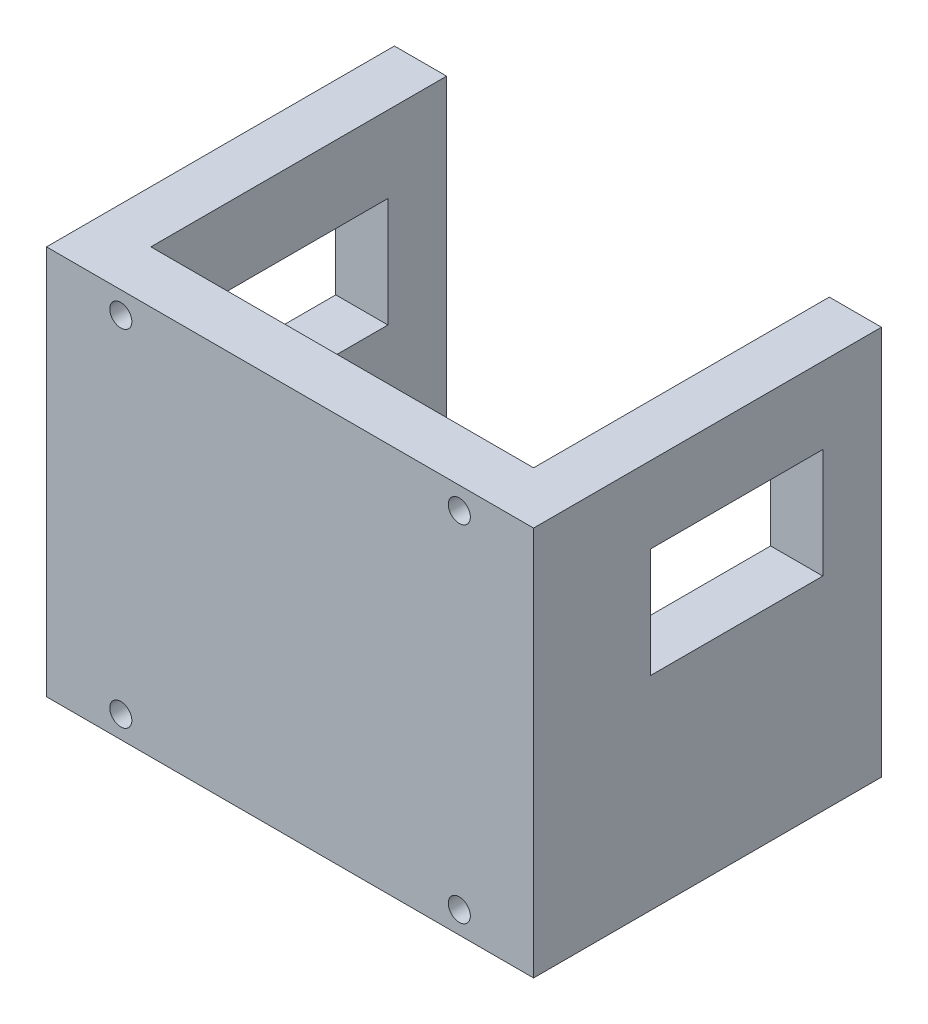
SolidWorks part; units mm, degrees
ref_plane "Plan de face" through (0, 0, 0) normal (0, 0, 1) x (1, 0, 0)
ref_plane "Plan de dessus" through (0, 0, 0) normal (0, 1, 0) x (1, 0, 0)
ref_plane "Plan de droite" through (0, 0, 0) normal (1, 0, 0) x (0, 0, -1)
sketch "Esquisse1" plane through (0, 0, 0) normal (0, 0, 1) x (1, 0, 0)
  line L0 (-109.5296, 4.4139) -> (30.4704, 4.4139)
  line L1 (-109.5296, 4.4139) -> (-109.5296, -107.5861)
  line L2 (-109.5296, -107.5861) -> (30.4704, -107.5861)
  line L3 (30.4704, -107.5861) -> (30.4704, 4.4139)
  point P4 (30.4704, 4.4139)
  dimension "D1" = 140
  dimension "D2" = 112
extrude "Boss.-Extru.1" add sketch "Esquisse1" along normal blind 100
sketch "Esquisse2" plane through (0, 4.4139, 0) normal (0, 1, 0) x (1, 0, 0)
  line L0 (30.4704, 0) -> (-109.5296, 0) construction
  line L1 (-94.5296, 0) -> (15.4704, 0)
  line L2 (-94.5296, 0) -> (-94.5296, -85)
  line L3 (-94.5296, -85) -> (15.4704, -85)
  line L4 (15.4704, 0) -> (15.4704, -85)
  line L5 (-109.5296, -100) -> (-109.5296, 0) construction
  line L6 (30.4704, -100) -> (-109.5296, -100) construction
  line L7 (30.4704, -100) -> (30.4704, 0) construction
  dimension "D1" = 15
  dimension "D2" = 15
  dimension "D3" = 15
extrude "Enlèv. mat.-Extru.1" cut sketch "Esquisse2" against normal through all contours L3 L4 L1 L2
sketch "Esquisse3" plane through (-109.5296, 0, 0) normal (-1, 0, 0) x (0, 0, 1)
  line L0 (58.0675, -19.0982) -> (25.1675, -19.0982) construction
  line L1 (16.8675, -49.0982) -> (66.3675, -49.0982)
  line L2 (16.8675, -49.0982) -> (16.8675, -17.5982)
  line L3 (16.8675, -17.5982) -> (66.3675, -17.5982)
  line L4 (66.3675, -49.0982) -> (66.3675, -17.5982)
  line L5 (64.8675, -40.7982) -> (64.8675, -25.8982) construction
  line L6 (25.1675, -47.5982) -> (58.0675, -47.5982) construction
  line L7 (18.3675, -29.3282) -> (18.3675, -37.3682) construction
  dimension "D1" = 1.5
  dimension "D2" = 1.5
  dimension "D3" = 1.5
  dimension "D4" = 1.5
extrude "Enlèv. mat.-Extru.2" cut sketch "Esquisse3" against normal through all
sketch "Esquisse4" plane through (0, 0, 85) normal (0, 0, -1) x (-1, 0, 0)
  line L0 (-15.4704, -107.5861) -> (-15.4704, 4.4139) construction
  line L1 (94.5296, 4.4139) -> (-15.4704, 4.4139) construction
  circle A0 centre (-9.1204, -1.9361) radius 3.175
  point P2 (0, 0)
  point P7 (-3.1018, -2.2686)
  point P10 (-8.4172, -3.6832)
  dimension "D1" = 6.35
  dimension "D2" = 6.35
  dimension "D3" = 6.35
extrude "Enlèv. mat.-Extru.3" cut sketch "Esquisse4" against normal through all
sketch "Esquisse6" plane through (0, 0, 85) normal (0, 0, -1) x (-1, 0, 0)
  line L0 (39.5296, 19.4457) -> (39.5296, -119.95) construction
  line L1 (-15.4704, -107.5861) -> (-15.4704, 4.4139) construction
  line L2 (-51.5517, -51.5861) -> (125.9992, -51.5861) construction
  line L4 (94.5296, 4.4139) -> (-15.4704, 4.4139) construction
  dimension "D1" = 55
  dimension "D2" = 56
ref_plane "Plan1" through (-39.5296, 0, 0) normal (1, 0, 0) x (0, -1, 0)
mirror "Symétrie1" about plane through (-39.5296, 0, 0) normal (1, 0, 0) of "Enlèv. mat.-Extru.3"
ref_plane "Plan2" through (0, -51.5861, 0) normal (0, -1, 0) x (-1, 0, 0)
mirror "Symétrie2" about plane through (0, -51.5861, 0) normal (0, -1, 0) of "Symétrie1", "Enlèv. mat.-Extru.3"
